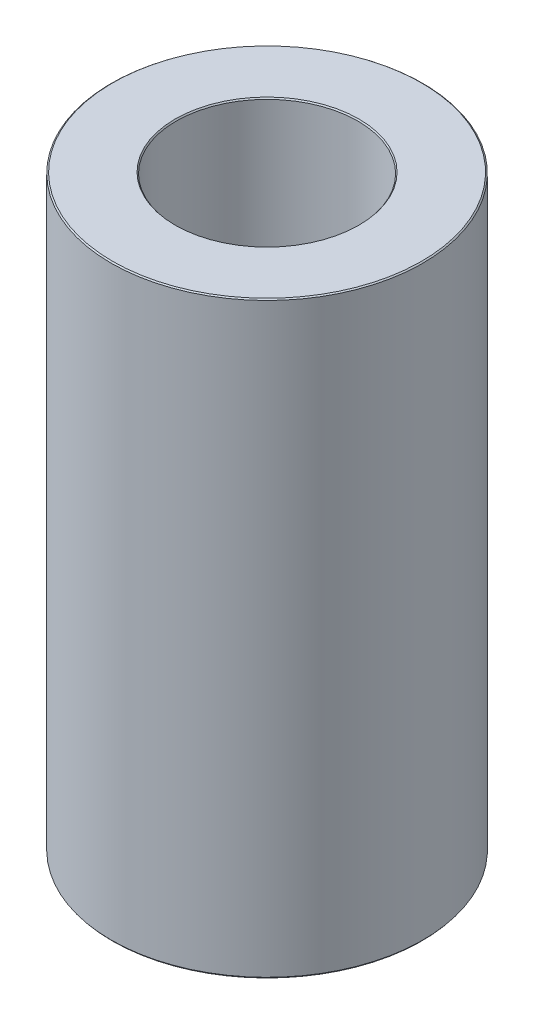
SolidWorks part; units mm, degrees
ref_plane "Front Plane" through (0, 0, 0) normal (0, 0, 1) x (1, 0, 0)
ref_plane "Top Plane" through (0, 0, 0) normal (0, 1, 0) x (1, 0, 0)
ref_plane "Right Plane" through (0, 0, 0) normal (1, 0, 0) x (0, 0, -1)
sketch "Sketch1" plane through (0, 0, 0) normal (0, 1, 0) x (1, 0, 0)
  circle A0 centre (0, 0) radius 50
  dimension "SLEEVE_OD" = 100
extrude "Boss-Extrude1" add sketch "Sketch1" along normal blind 188.8655
sketch "Sketch2" plane through (0, 0, 0) normal (0, 1, 0) x (1, 0, 0)
  circle A0 centre (0, 0) radius 29.1768
  dimension "BORE_D" = 58.3537
extrude "Cut-Extrude1" cut sketch "Sketch2" along normal through all
chamfer "Chamfer1" distance 0.3286 angle 51.474 4 edges at (0, 188.8655, 29.1768) (0, 0, 29.1768) (0, 0, 50) (0, 188.8655, 50) first distance on face at (0, 188.8655, 29.1768) first distance on face at (0, 0, 29.1768) first distance on face at (0, 188.8655, 50)
